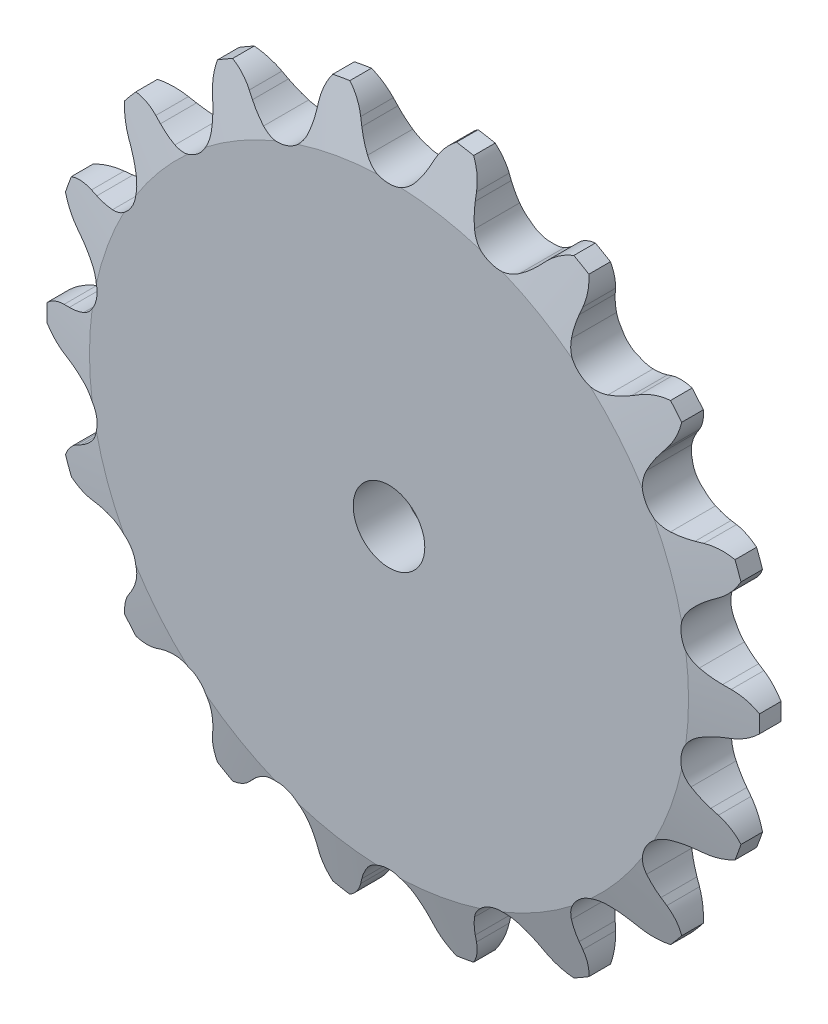
SolidWorks part; units mm, degrees
ref_plane "Front Plane" through (0, 0, 0) normal (0, 0, 1) x (1, 0, 0)
ref_plane "Top Plane" through (0, 0, 0) normal (0, 1, 0) x (1, 0, 0)
ref_plane "Right Plane" through (0, 0, 0) normal (1, 0, 0) x (0, 0, -1)
ref_axis "Axis1" through (0, 0, -88.99) along (0, 0, 1)
sketch "Sprocket-BaseSketch" plane through (0, 0, 0) normal (1, 0, 0) x (0, 0, -1)
  line L0 (1.397, 0) -> (1.397, 16.7363)
  line L1 (1.397, 16.7363) -> (0.6032, 19.9113)
  line L2 (0.6032, 19.9113) -> (-0.6032, 19.9113)
  line L3 (-0.6032, 19.9113) -> (-1.397, 16.7363)
  line L4 (-1.397, 16.7363) -> (-1.397, 0)
  line L5 (-1.397, 0) -> (1.397, 0)
  line L6 (5.588, 0) -> (-1.7463, 0) construction
  dimension "Hub Surface" = 1.397
  dimension "RightSide (1)" = 0.7938
  dimension "RightSide (2)" = 3.175
  dimension "OD" = 19.9113
  dimension "LeftSide (1)" = 0.7938
  dimension "LeftSide (2)" = 3.175
  dimension "Tooth Width" = 2.794
revolve "25 (04C) ANSI (ISO) Chain Number, 1.440in P.D." add sketch "Sprocket-BaseSketch" angle 360 about L6
sketch "Tooth-Sketch" plane through (0, 0, 0) normal (0, 0, 1) x (1, 0, 0)
  line L0 (0, 0) -> (0, 24.3788) construction
  line L1 (1.9086, 18.1962) -> (2.0662, 18.5596)
  line L2 (-1.9086, 18.1962) -> (-2.0662, 18.5596)
  line L3 (0, 18.2841) -> (6.2535, 17.1814) construction
  line L4 (0, 18.2841) -> (-6.2535, 17.1814) construction
  arc A0 (-1.3314, 17.2313) -> (1.3314, 17.2313) centre (0, 18.2841) ccw
  arc A1 (1.3314, 17.2313) -> (1.9086, 18.1962) centre (-2.0721, 19.9225) ccw
  arc A2 (-1.3314, 17.2313) -> (-1.9086, 18.1962) centre (2.0721, 19.9225) cw
  arc A3 (2.0662, 18.5596) -> (4.5526, 20.1914) centre (4.5526, 17.4814) cw
  arc A4 (-2.0662, 18.5596) -> (-4.5526, 20.1914) centre (-4.5526, 17.4814) ccw
  arc A5 (4.5526, 20.1914) -> (-4.5526, 20.1914) centre (0, 0) ccw
extrude "Tooth-Cut, Number of teeth: 18" cut sketch "Tooth-Sketch" against normal through all and the other way through all
pattern_circular "Tooth Pattern, 18 / 18" count 18 every 20 about axis through (0, 0, -88.99) along (0, 0, 1) of "Tooth-Cut, Number of teeth: 18"
sketch "Sketch4" plane through (0, 0, 0) normal (0, 0, 1) x (1, 0, 0)
  circle A0 centre (0, 0) radius 2
  dimension "D1" = 4
extrude "Cut-Extrude1" cut sketch "Sketch4" against normal through all and the other way through all
sketch "Sketch5" plane through (0, 0, 0) normal (0, 0, 1) x (1, 0, 0)
  circle A0 centre (0, 0) radius 19.9113
  dimension "D1" = 39.8226
equation "\"D1@Sketch5\" = \"OD@Sprocket-BaseSketch\"*2"
